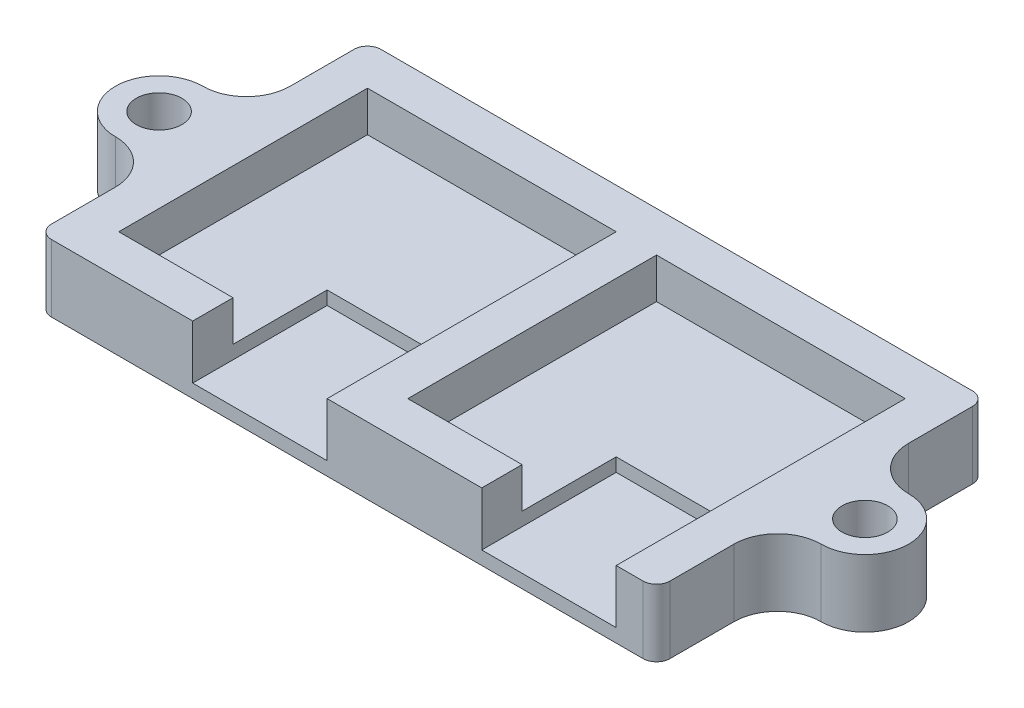
SolidWorks part; units mm, degrees
ref_plane "Спереди" through (0, 0, 0) normal (0, 0, 1) x (1, 0, 0)
ref_plane "Сверху" through (0, 0, 0) normal (0, 1, 0) x (1, 0, 0)
ref_plane "Справа" through (0, 0, 0) normal (1, 0, 0) x (0, 0, -1)
sketch "Эскиз1" plane through (0, 0, 0) normal (0, 1, 0) x (1, 0, 0)
  line L0 (-117.532, 0) -> (5759.069, 0) construction
  line L1 (0, -117.532) -> (0, 5759.069) construction
  line L2 (-10.75, -118.4842) -> (-10.75, 5758.1169) construction
  line L3 (22, -12.25) -> (-22, -12.25)
  line L4 (23, -11.25) -> (23, 11.25)
  line L5 (22, 12.25) -> (-22, 12.25)
  line L6 (-23, -11.25) -> (-23, 11.25)
  line L7 (23, -12.25) -> (-23, 12.25) construction
  line L8 (23, 12.25) -> (-23, -12.25) construction
  line L9 (10.75, -118.0956) -> (10.75, 5758.5055) construction
  line L10 (-1.5, 12.25) -> (-1.5, 9.25) construction
  line L11 (-20, 9.25) -> (-1.5, 9.25)
  line L12 (-20, 9.25) -> (-20, -9.25)
  line L13 (-20, -9.25) -> (-1.5, -9.25)
  line L14 (-1.5, 9.25) -> (-1.5, -9.25)
  line L15 (-20, 9.25) -> (-1.5, -9.25) construction
  line L16 (-20, -9.25) -> (-1.5, 9.25) construction
  line L17 (1.5, 9.25) -> (20, 9.25)
  line L18 (1.5, 9.25) -> (1.5, -9.25)
  line L19 (1.5, -9.25) -> (20, -9.25)
  line L20 (20, 9.25) -> (20, -9.25)
  line L21 (1.5, 9.25) -> (20, -9.25) construction
  line L22 (1.5, -9.25) -> (20, 9.25) construction
  line L23 (1.5, 9.25) -> (-1.5, 9.25) construction
  line L24 (20, 9.25) -> (23, 9.25) construction
  line L26 (-1.5, -12.25) -> (-11.5, -12.25)
  line L27 (-1.5, -12.25) -> (-1.5, -2.25)
  line L28 (-1.5, -2.25) -> (-11.5, -2.25)
  line L29 (-11.5, -12.25) -> (-11.5, -2.25)
  line L30 (20, -12.25) -> (10, -12.25)
  line L31 (20, -12.25) -> (20, -2.25)
  line L32 (20, -2.25) -> (10, -2.25)
  line L33 (10, -12.25) -> (10, -2.25)
  arc A0 (-26.25, 3.25) -> (-26.25, -3.25) centre (-26.25, 0) ccw
  circle A1 centre (-26.25, 0) radius 1.7
  arc A6 (-26.25, 3.25) -> (-23, 6.5) centre (-26.25, 6.5) ccw
  arc A7 (-23, -6.5) -> (-26.25, -3.25) centre (-26.25, -6.5) ccw
  circle A8 centre (26.25, 0) radius 1.7
  arc A9 (23, -6.5) -> (26.25, -3.25) centre (26.25, -6.5) cw
  arc A10 (26.25, 3.25) -> (23, 6.5) centre (26.25, 6.5) cw
  arc A11 (26.25, 3.25) -> (26.25, -3.25) centre (26.25, 0) cw
  arc A12 (-22, -12.25) -> (-23, -11.25) centre (-22, -11.25) cw
  arc A13 (22, -12.25) -> (23, -11.25) centre (22, -11.25) ccw
  arc A14 (23, 11.25) -> (22, 12.25) centre (22, 11.25) ccw
  arc A15 (-22, 12.25) -> (-23, 11.25) centre (-22, 11.25) ccw
  point P4 (0, 0)
  point P13 (-10.75, 0)
  point P19 (10.75, 0)
  point P24 (0, -12.25)
  point P25 (-10.75, 12.25)
  point P26 (10.75, 12.25)
  point P28 (0, 12.25)
  dimension "D3" = 3.4
  dimension "D4" = 6.5
  dimension "D6" = 1
  dimension "D1" = 24.5
  dimension "D2" = 18.5
  dimension "D5" = 10
extrude "Бобышка-Вытянуть1" add sketch "Эскиз1" along normal blind 1 contours A7 L6 A6 A0 A1 | L5 A15 L6 A12 L3 L29 L13 L12 L11 L14 L27 L33 L19 L18 L17 L20 L31 A13 L4 A14 | L29 L3 L27 L13 | L29 L13 L14 L28 | L13 L29 L28 L14 L11 L12 | L19 L33 L32 L20 L17 L18 | L33 L3 L31 L19 | L33 L19 L20 L32 | A11 A10 L4 A9 A8 region at (-0.6682, 0, -1.6901) region at (15, 0, 10.75) region at (15, 0, 5.75) region at (23.1453, 0, 0) region at (-6.5, 0, 10.75) region at (9.6573, 0, -1.4784) region at (-6.5, 0, 5.75) region at (-11.8427, 0, -1.4784) region at (-23.8491, 0, 4.0991)
extrude "Бобышка-Вытянуть2" add sketch "Эскиз1<3>" along normal blind 1 from surface contours L5 A15 L6 A12 L3 L29 L13 L12 L11 L14 L27 L33 L19 L18 L17 L20 L31 A13 L4 A14 | L13 L29 L28 L14 L11 L12 | A7 L6 A6 A0 A1 | L19 L33 L32 L20 L17 L18 | A11 A10 L4 A9 A8 region at (-0.6682, 0, -1.6901) region at (23.1453, 0, 0) region at (9.6573, 0, -1.4784) region at (-11.8427, 0, -1.4784) region at (-23.8491, 0, 4.0991) starting at face at (0, 1, 0)
sketch "Эскиз1<3>" plane through (0, 0, 0) normal (0, 1, 0) x (1, 0, 0) same geometry as "Эскиз1"
extrude "Бобышка-Вытянуть3" add sketch "Эскиз1<5>" along normal blind 3 from surface contours L5 A15 L6 A12 L3 L29 L13 L12 L11 L14 L27 L33 L19 L18 L17 L20 L31 A13 L4 A14 | A7 L6 A6 A0 A1 | A11 A10 L4 A9 A8 region at (-0.6682, 0, -1.6901) region at (23.1453, 0, 0) region at (-23.8491, 0, 4.0991) starting at face at (26.25, 2, 1.7)
sketch "Эскиз1<5>" plane through (0, 0, 0) normal (0, 1, 0) x (1, 0, 0) same geometry as "Эскиз1"
extrude "Бобышка-Вытянуть4" add sketch "Эскиз1<7>" along normal blind 2.5 from offset 7 separate body contours L5 A15 L6 A12 L3 L29 L13 L12 L11 L14 L27 L33 L19 L18 L17 L20 L31 A13 L4 A14 | A7 L6 A6 A0 A1 | A11 A10 L4 A9 A8 | L29 L3 L27 L13 | L33 L3 L31 L19 region at (-0.6682, 0, -1.6901) region at (15, 0, 10.75) region at (23.1453, 0, 0) region at (-6.5, 0, 10.75) region at (-23.8491, 0, 4.0991)
sketch "Эскиз1<7>" plane through (0, 0, 0) normal (0, 1, 0) x (1, 0, 0) same geometry as "Эскиз1"
extrude "Бобышка-Вытянуть5" add sketch "Эскиз1<9>" along normal blind 1 from surface contours L13 L29 L28 L14 L11 L12 | L19 L33 L32 L20 L17 L18 | L33 L19 L20 L32 | L33 L3 L31 L19 | L29 L3 L27 L13 | L29 L13 L14 L28 | L5 A15 L6 A12 L3 L29 L13 L12 L11 L14 L27 L33 L19 L18 L17 L20 L31 A13 L4 A14 | A11 A10 L4 A9 A8 | A7 L6 A6 A0 A1 region at (-0.6682, 0, -1.6901) region at (15, 0, 10.75) region at (15, 0, 5.75) region at (23.1453, 0, 0) region at (-6.5, 0, 10.75) region at (9.6573, 0, -1.4784) region at (-6.5, 0, 5.75) region at (-11.8427, 0, -1.4784) region at (-23.8491, 0, 4.0991) starting at face at (-10.75, 9.5, 0)
sketch "Эскиз1<9>" plane through (0, 0, 0) normal (0, 1, 0) x (1, 0, 0) same geometry as "Эскиз1"
fillet "Скругление1" radius 1 16 edges at (-22.7071, 10.5, 11.9571) (-23, 10.5, 8.875) (-23.9519, 10.5, 4.2019) (-29.5, 10.5, 0) (-23.9519, 10.5, -4.2019) (-23, 10.5, -8.875) (-22.7071, 10.5, -11.9571) (0, 10.5, -12.25) (22.7071, 10.5, -11.9571) (23, 10.5, -8.875) (23.9519, 10.5, -4.2019) (29.5, 10.5, 0) (23.9519, 10.5, 4.2019) (23, 10.5, 8.875) (22.7071, 10.5, 11.9571) (0, 10.5, 12.25)
delete or keep bodies "Тело-Удалить/Сохранить 1" type keep bodies bodies 103
